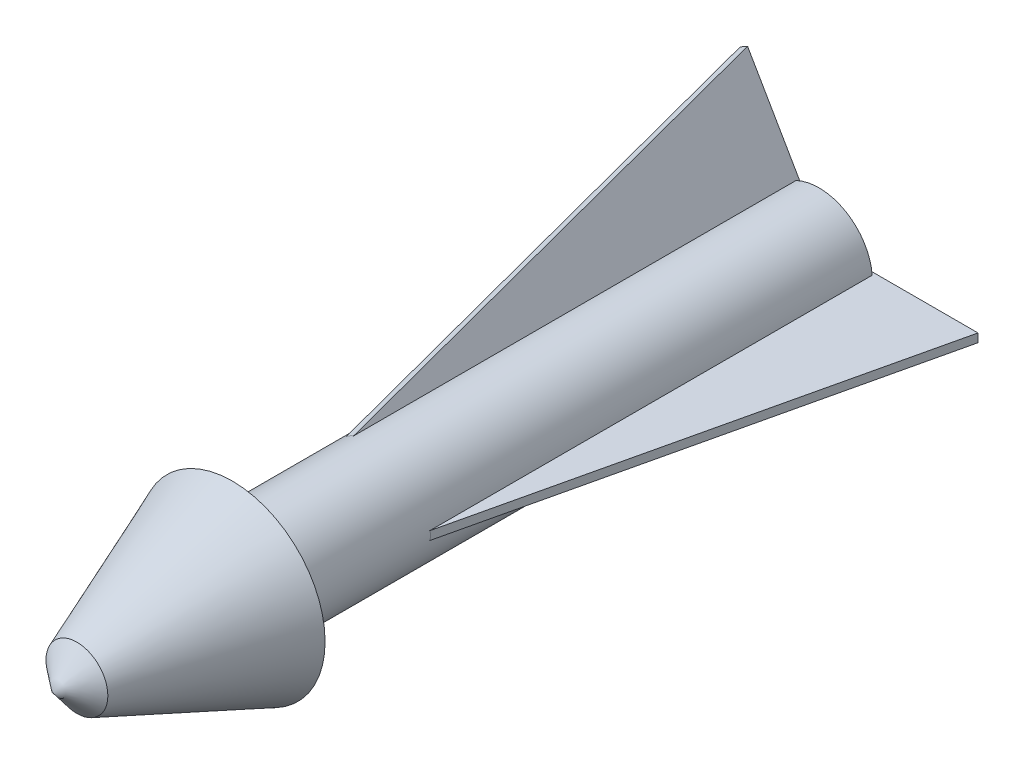
SolidWorks part; units mm, degrees
ref_plane "Front Plane" through (0, 0, 0) normal (0, 0, 1) x (1, 0, 0)
ref_plane "Top Plane" through (0, 0, 0) normal (0, 1, 0) x (1, 0, 0)
ref_plane "Right Plane" through (0, 0, 0) normal (1, 0, 0) x (0, 0, -1)
sketch "Sketch1" plane through (0, 0, 0) normal (1, 0, 0) x (0, 0, -1)
  line L0 (-44.6785, 0) -> (48.3506, 0) construction
  line L1 (6.8356, 0) -> (6.8356, 4.933)
  line L2 (6.8356, 4.933) -> (56.8356, 4.933)
  line L3 (56.8356, 4.933) -> (56.8356, 6.2668)
  line L4 (56.8356, 6.2668) -> (-11.9935, 6.2668)
  line L5 (-11.9935, 6.2668) -> (-11.9935, 10.8766)
  line L7 (-33.1644, 0) -> (6.8356, 0)
  line L8 (-11.9935, 10.8766) -> (-30.2386, 3.6282)
  line L9 (-30.2386, 3.6282) -> (-33.1644, 0)
  dimension "D1" = 40
  dimension "D2" = 50
  dimension "D3" = 4.933
revolve "Revolve2" add sketch "Sketch1" angle 360 about L0
fillet "Fillet1" radius 3 1 edges at (6.2668, 0, 11.9935)
sketch "Sketch2" plane through (0, 0, 0) normal (0, 1, 0) x (1, 0, 0)
  line L0 (5.5752, 1.9971) -> (18.3156, 57.182)
  line L2 (18.3156, 57.182) -> (5.5752, 57.182)
  line L3 (5.5752, 57.182) -> (5.5752, 1.9971)
  point P6 (0, 0)
  dimension "D1" = 13
extrude "Boss-Extrude2" add sketch "Sketch2" along normal mid plane 1 contours L3 L0 L2
ref_axis "Axis2" through (0, 0, -56.8356) along (0, 0, 1)
pattern_circular "CirPattern3" count 3 over 360 about axis through (0, 0, -56.8356) along (0, 0, 1) of "Boss-Extrude2"
